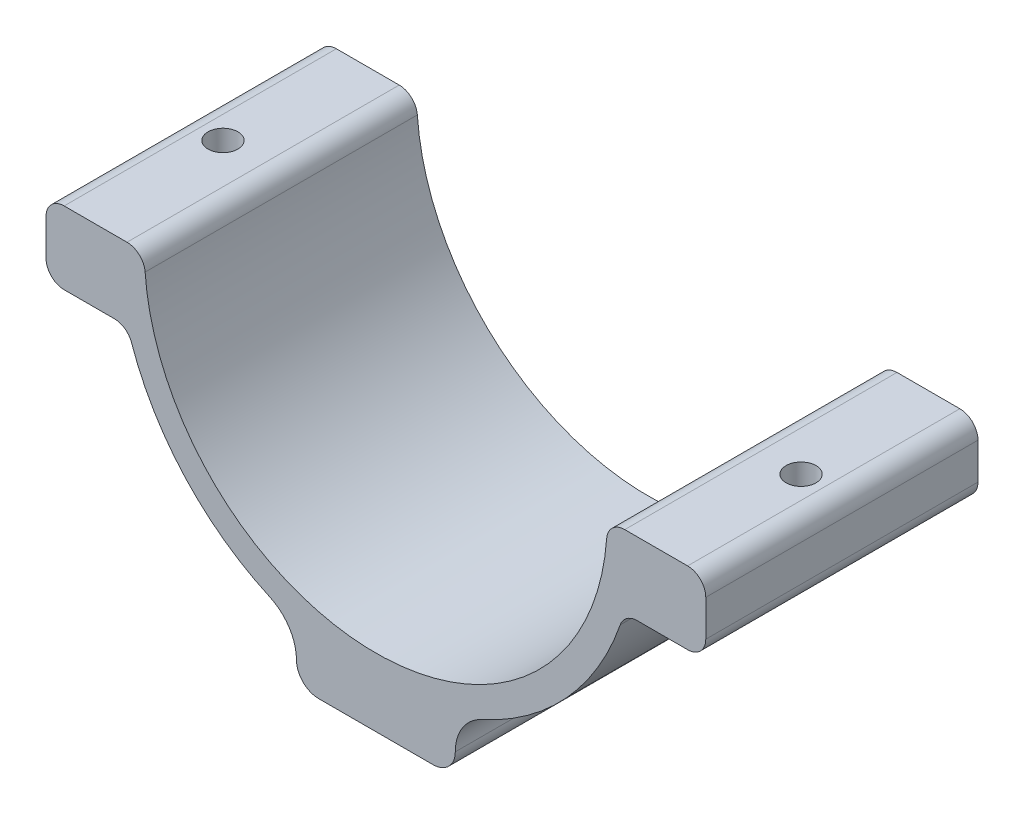
SolidWorks part; units mm, degrees
ref_plane "Front Plane" through (0, 0, 0) normal (0, 0, 1) x (1, 0, 0)
ref_plane "Top Plane" through (0, 0, 0) normal (0, 1, 0) x (1, 0, 0)
ref_plane "Right Plane" through (0, 0, 0) normal (1, 0, 0) x (0, 0, -1)
sketch "Sketch2" plane through (0, 0, 0) normal (0, 0, 1) x (1, 0, 0)
  circle A0 centre (0, 0) radius 25.2 construction
  dimension "D1" = 50.4
sketch "Sketch3" plane through (0, 0, 0) normal (0, 0, 1) x (1, 0, 0)
  line L0 (-25.5, 0) -> (-36.3542, 0)
  line L1 (25.5, 0) -> (36.3542, 0)
  line L7 (-11, -26.2916) -> (-11, -73.6)
  line L8 (-11, -73.6) -> (11, -73.6)
  line L9 (11, -73.6) -> (11, -26.2916)
  line L11 (27.3542, -8) -> (36.3542, -8)
  line L12 (36.3542, -8) -> (36.3542, 0)
  line L13 (-27.3542, -8) -> (-36.3542, -8)
  line L14 (-36.3542, -8) -> (-36.3542, 0)
  line L15 (31.8542, -8) -> (31.8542, 0) construction
  line L16 (28.8542, -4) -> (34.8542, -4) construction
  circle A1 centre (0, -62.6) radius 4 construction
  arc A2 (25.5, 0) -> (-25.5, 0) centre (0, 0) cw
  circle A3 centre (0, 0) radius 25.2 construction
  circle A7 centre (0, -62.6) radius 8.05
  arc A8 (11, -26.2916) -> (27.3542, -8) centre (0, 0) ccw
  arc A9 (-11, -26.2916) -> (-27.3542, -8) centre (0, 0) cw
  point P9 (0, -73.6)
  point P24 (31.8542, -4)
  dimension "D1" = 0.3
  dimension "D3" = 37.4
  dimension "D4" = 8
  dimension "D5" = 16.1
  dimension "D7" = 3
  dimension "D2" = 48.4
  dimension "D6" = 22
  dimension "D8" = 8
  dimension "D9" = 6
  dimension "D10" = 1.5
  dimension "D11" = 1.5
  dimension "D12" = 0
extrude "Boss-Extrude1" add sketch "Sketch3" along normal blind 30
sketch "Sketch4" plane through (0, 0, 0) normal (0, 0, 1) x (1, 0, 0)
  circle A0 centre (0, -62.6) radius 8.05 construction
  circle A1 centre (0, -62.6) radius 8.05
  circle A2 centre (0, -62.6) radius 4.3
  dimension "D1" = 8.6
extrude "Boss-Extrude2" add sketch "Sketch4" along normal offset from surface (25 mm away) 5 up to face at (0, -21.7486, 30)
chamfer "Chamfer1" distance 3 angle 45 1 edges at (0, -73.6, 0)
fillet "Fillet1" radius 11 2 edges at (-11, -73.6, 16.5) (11, -73.6, 16.5)
sketch "Sketch5" plane through (0, -8, 0) normal (0, -1, 0) x (1, 0, 0)
  line L0 (28.8542, 0) -> (34.8542, 0) construction
  line L1 (28.8542, 0) -> (34.8542, 0) construction
  line L2 (31.8542, 0) -> (31.8542, 30) construction
  line L3 (36.3542, 30) -> (25.5, 30) construction
  line L4 (0, 0) -> (0, 30) construction
  line L5 (25.2, 0) -> (-25.2, 0) construction
  line L6 (25.5, 30) -> (-25.5, 30) construction
  circle A0 centre (31.8542, 15) radius 1.65
  dimension "D1" = 3.3
extrude "Cut-Extrude1" cut sketch "Sketch5" against normal through all
sketch "Sketch6" plane through (0, -8, 0) normal (0, -1, 0) x (1, 0, 0)
  circle A0 centre (31.8542, 15) radius 3
  dimension "D1" = 6
extrude "Cut-Extrude2" cut sketch "Sketch6" against normal blind 3
mirror "Mirror1" about plane through (0, 0, 0) normal (1, 0, 0) of "Cut-Extrude2", "Cut-Extrude1"
sketch "Sketch7" plane through (0, 0, 30) normal (0, 0, 1) x (1, 0, 0)
  line L0 (-11, -26.2916) -> (-11, -62.6) construction
  line L1 (-11, -55) -> (11, -55)
  line L2 (-11, -55) -> (-11, -73.6)
  line L3 (-11, -73.6) -> (11, -73.6)
  line L4 (11, -55) -> (11, -73.6)
  line L5 (-11, -55) -> (11, -73.6) construction
  line L6 (-11, -73.6) -> (11, -55) construction
  line L7 (11, -62.6) -> (11, -26.2916) construction
  point P4 (0, -64.3)
  dimension "D1" = 55
extrude "Cut-Extrude3" cut sketch "Sketch7" against normal through all
fillet "Fillet2" radius 2 8 edges at (-27.3542, -8, 15) (-36.3542, 0, 15) (-25.5, 0, 15) (25.5, 0, 15) (36.3542, 0, 15) (36.3542, -8, 15) (27.3542, -8, 15) (-36.3542, -8, 15)
sketch "Sketch8" plane through (0, 0, 30) normal (0, 0, 1) x (1, 0, 0)
  line L0 (-4.5, -49) -> (4.5, -49) construction
  circle A2 centre (4.5, -49) radius 1.65
  circle A3 centre (-4.5, -49) radius 1.65
  point P3 (0, -49)
  dimension "D1" = 3.3
  dimension "D2" = 9
  dimension "D3" = 49
extrude "Cut-Extrude4" cut sketch "Sketch8" against normal through all
sketch "Sketch9" plane through (0, 0, 30) normal (0, 0, 1) x (1, 0, 0)
  line L0 (-8.75, -55) -> (-8.75, -27.1236)
  line L1 (11, -55) -> (2.6538, -55) construction
  line L2 (8.75, -55) -> (8.75, -27.1236)
  line L3 (-8.75, -41.0618) -> (8.75, -41.0618) construction
  line L4 (-11, -26.2916) -> (-11, -55)
  line L5 (-11, -55) -> (-8.75, -55)
  line L6 (8.75, -55) -> (11, -55)
  line L7 (11, -55) -> (11, -26.2916)
  arc A0 (-8.75, -27.1236) -> (-11, -26.2916) centre (0, 0) cw
  arc A1 (8.75, -27.1236) -> (11, -26.2916) centre (0, 0) ccw
  arc A2 (11, -26.2916) -> (26.9246, -9.3443) centre (0, 0) ccw construction
  point P10 (0, -41.0618)
  dimension "D1" = 17.5
extrude "Cut-Extrude5" cut sketch "Sketch9" against normal through all
fillet "Fillet3" radius 5 4 edges at (-8.75, -55, 15) (8.75, -55, 15) (8.75, -27.1236, 15) (-8.75, -27.1236, 15)
sketch "Sketch10" plane through (0, 0, 30) normal (0, 0, 1) x (1, 0, 0)
  circle A0 centre (4.5, -49) radius 3
  circle A1 centre (-4.5, -49) radius 3
  dimension "D1" = 6
extrude "Cut-Extrude6" cut sketch "Sketch10" against normal blind 3
sketch "Sketch11" plane through (0, 0, 30) normal (0, 0, 1) x (1, 0, 0)
  line L0 (-6.6, -34.0716) -> (-2.4, -34.0716) construction
  line L1 (2.4, -34.0716) -> (6.6, -34.0716) construction
  line L2 (-4.5, -34.0716) -> (-4.5, -32.2282) construction
  line L3 (-4.5, -32.2282) -> (4.5, -32.2282) construction
  line L4 (4.5, -32.2282) -> (4.5, -34.0716) construction
  line L5 (8.75, -30.5481) -> (8.75, -50) construction
  line L6 (3.75, -55) -> (-3.75, -55) construction
  line L7 (-8.75, -50) -> (-8.75, -30.5481) construction
  line L8 (8.75, -30.5481) -> (8.75, -50)
  line L9 (3.75, -55) -> (-3.75, -55)
  line L10 (-8.75, -50) -> (-8.75, -30.5481)
  line L11 (-6.2981, -33) -> (6.2981, -33)
  arc A2 (3.75, -55) -> (8.75, -50) centre (3.75, -50) ccw construction
  arc A3 (-8.75, -50) -> (-3.75, -55) centre (-3.75, -50) ccw construction
  arc A4 (3.75, -55) -> (8.75, -50) centre (3.75, -50) ccw
  arc A5 (-8.75, -50) -> (-3.75, -55) centre (-3.75, -50) ccw
  arc A6 (-8.75, -30.5481) -> (-6.2981, -33) centre (-6.2981, -30.5481) ccw
  arc A7 (6.2981, -33) -> (8.75, -30.5481) centre (6.2981, -30.5481) ccw
  point P9 (0, -32.2282)
  dimension "D1" = 4.2
  dimension "D2" = 9
  dimension "D3" = 33
extrude "Cut-Extrude7" cut sketch "Sketch11" against normal through all
sketch "Sketch12" plane through (0, -33, 0) normal (0, -1, 0) x (1, 0, 0)
  line L0 (-4.5, 15) -> (4.5, 15) construction
  line L1 (-8.75, 30) -> (-8.75, 0) construction
  line L2 (-8.75, 30) -> (-8.75, 0) construction
  circle A0 centre (-4.5, 15) radius 2.1
  circle A1 centre (4.5, 15) radius 2.1
  point P4 (0, 15)
  point P9 (-8.75, 15)
  dimension "D1" = 4.2
  dimension "D2" = 9
extrude "Cut-Extrude8" cut sketch "Sketch12" against normal blind 5
